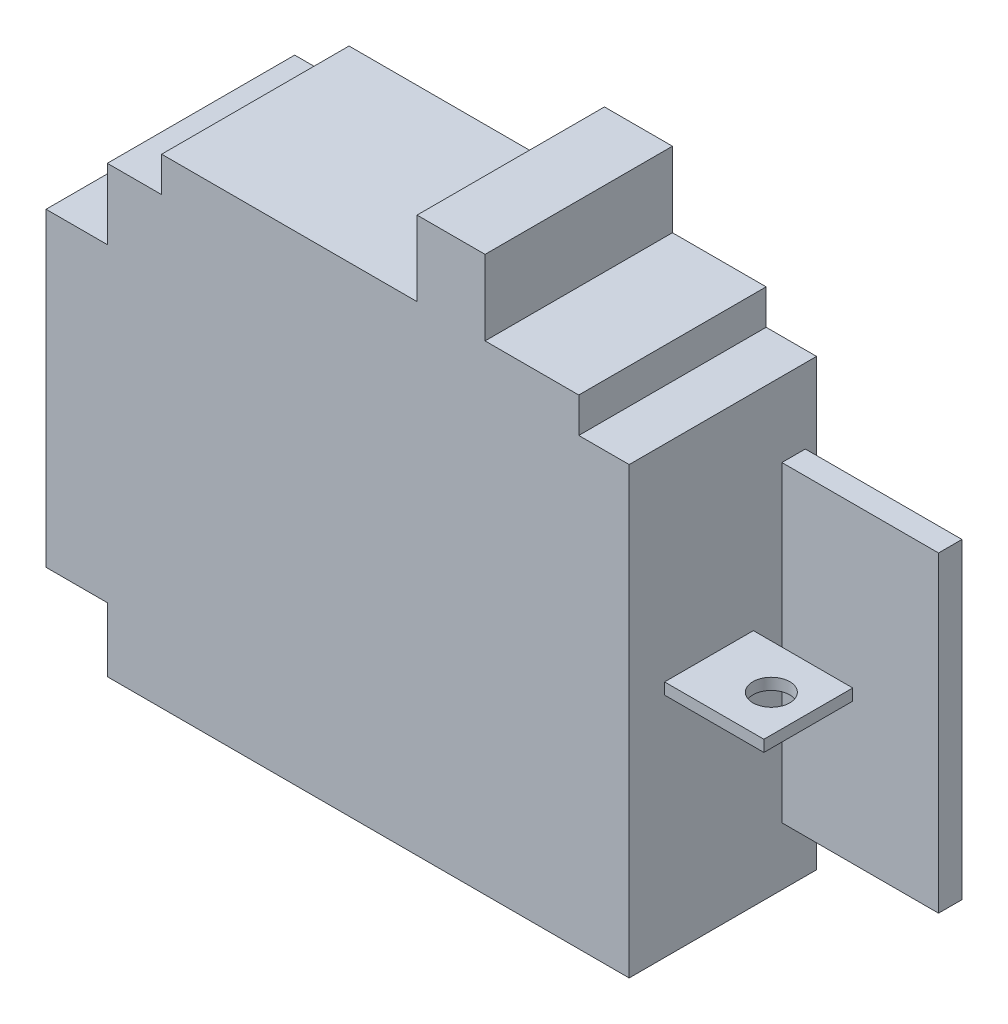
SolidWorks part; units mm, degrees
ref_plane "Front Plane" through (0, 0, 0) normal (0, 0, 1) x (1, 0, 0)
ref_plane "Top Plane" through (0, 0, 0) normal (0, 1, 0) x (1, 0, 0)
ref_plane "Right Plane" through (0, 0, 0) normal (1, 0, 0) x (0, 0, -1)
sketch "Sketch1" plane through (0, 0, 0) normal (0, 0, 1) x (1, 0, 0)
  line L0 (28.5369, 30.1371) -> (35.3695, 30.1371)
  line L1 (-35.3695, -30.1371) -> (35.3695, -30.1371)
  line L2 (-35.3695, -30.1371) -> (-35.3695, -21.4503)
  line L3 (-35.3695, 30.1371) -> (-28.0035, 30.1371)
  line L4 (35.3695, -30.1371) -> (35.3695, 30.1371)
  line L5 (-35.3695, -30.1371) -> (35.3695, 30.1371) construction
  line L6 (-35.3695, 30.1371) -> (35.3695, -30.1371) construction
  line L7 (-35.3695, -21.4503) -> (-43.6753, -21.4503)
  line L8 (-43.6753, -21.4503) -> (-43.6753, 20.5867)
  line L9 (-43.6753, 20.5867) -> (-35.3695, 20.5867)
  line L10 (-35.3695, 20.5867) -> (-35.3695, 30.1371)
  line L11 (-28.0035, 30.1371) -> (-28.0035, 34.8869)
  line L13 (28.5369, 34.8869) -> (28.5369, 30.1371)
  line L14 (28.5369, 34.8869) -> (15.8369, 34.8869)
  line L15 (15.8369, 34.8869) -> (15.8369, 45.0469)
  line L16 (15.8369, 45.0469) -> (6.6167, 45.0469)
  line L17 (6.6167, 45.0469) -> (6.6167, 34.8869)
  line L18 (6.6167, 34.8869) -> (-28.0035, 34.8869)
  point P0 (0, 0)
  dimension "D1" = 70.739
extrude "Boss-Extrude1" add sketch "Sketch1" along normal blind 25.4 contours L18 L11 L3 L10 L9 L8 L7 L2 L1 L4 L0 L13 L14 L15 L16 L17
sketch "Sketch2" plane through (35.3695, 0, 0) normal (1, 0, 0) x (0, 0, -1)
  line L0 (0, 30.1371) -> (-1.524, 30.1371)
  line L1 (-25.4, 30.1371) -> (0, 30.1371) construction
  line L2 (-1.524, 30.1371) -> (-1.524, 20.0257)
  line L10 (-1.524, 20.0257) -> (-4.699, 20.0257)
  line L11 (-1.524, 20.0257) -> (-1.524, -22.2653)
  line L12 (-1.524, -22.2653) -> (-4.699, -22.2653)
  line L13 (-4.699, 20.0257) -> (-4.699, -22.2653)
extrude "Boss-Extrude2" add sketch "Sketch2" along normal blind 21.2344 contours L11 L10 L13 L12
sketch "Sketch3" plane through (35.3695, 0, 0) normal (1, 0, 0) x (0, 0, -1)
  line L0 (-25.4, 30.1371) -> (-25.4, 0.6731)
  line L1 (-25.4, -30.1371) -> (-25.4, 30.1371) construction
  line L6 (-8.5598, 2.2225) -> (-20.5994, 2.2225)
  line L7 (-8.5598, 2.2225) -> (-8.5598, 0.6731)
  line L8 (-8.5598, 0.6731) -> (-20.5994, 0.6731)
  line L9 (-20.5994, 2.2225) -> (-20.5994, 0.6731)
extrude "Boss-Extrude3" add sketch "Sketch3" along normal blind 13.462 contours L7 L6 L9 L8
sketch "Sketch4" plane through (0, 2.2225, 0) normal (0, 1, 0) x (1, 0, 0)
  circle A0 centre (43.8213, -14.5796) radius 2.4955
  point P0 (0, 0)
extrude "Cut-Extrude1" cut sketch "Sketch4" against normal blind 16.51
